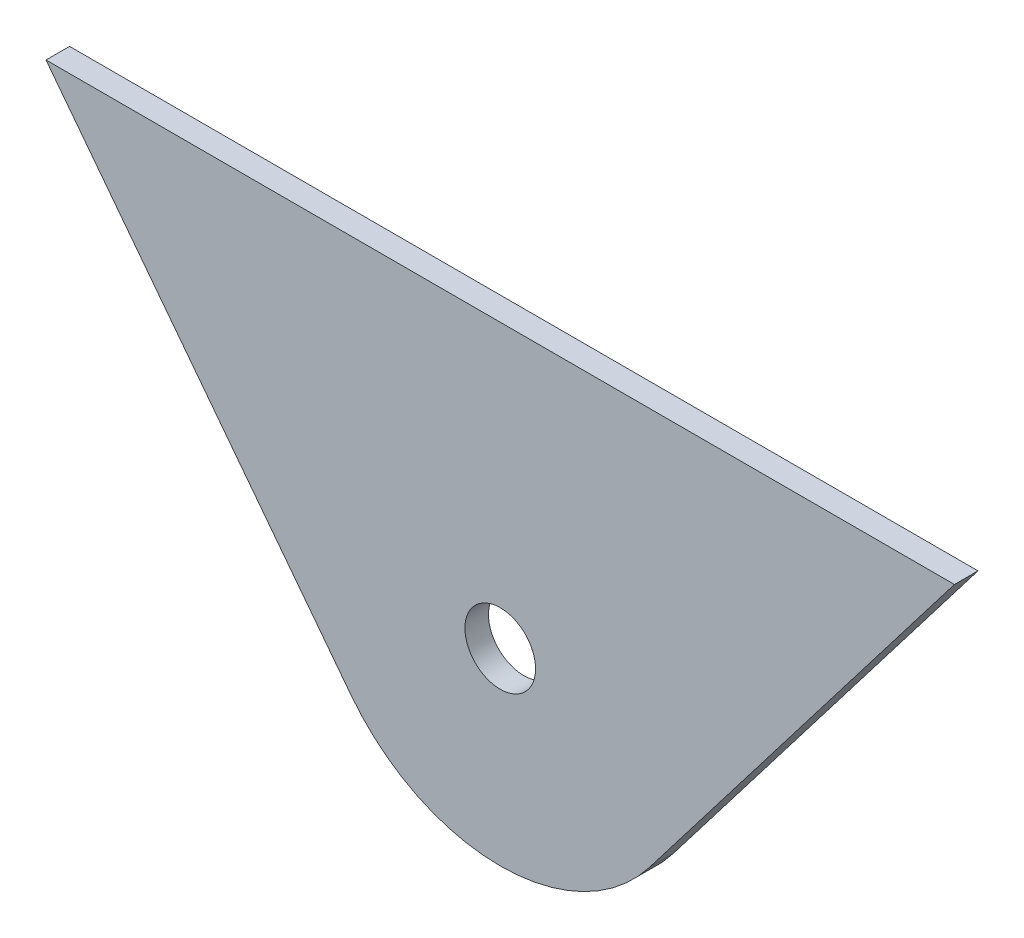
SolidWorks part; units mm, degrees
ref_plane "Front Plane" through (0, 0, 0) normal (0, 0, 1) x (1, 0, 0)
ref_plane "Top Plane" through (0, 0, 0) normal (0, 1, 0) x (1, 0, 0)
ref_plane "Right Plane" through (0, 0, 0) normal (1, 0, 0) x (0, 0, -1)
ref_axis "Suspension pivot point" through (0, 0, -0.1588) along (0, 0, 1)
sketch "Sketch1" plane through (0, 0, 0) normal (0, 0, 1) x (1, 0, 0)
  line L0 (-20.1512, -15.4625) -> (-61.2512, 38.1)
  line L1 (-61.2512, 38.1) -> (61.2512, 38.1)
  line L2 (61.2512, 38.1) -> (20.1512, -15.4625)
  line L3 (0, -25.4) -> (0, 38.1) construction
  arc A0 (-20.1512, -15.4625) -> (20.1512, -15.4625) centre (0, 0) ccw
  dimension "D1" = 25.4
  dimension "D2" = 75
  dimension "D3" = 63.5
extrude "Boss-Extrude1" add sketch "Sketch1" along normal blind 3.175
sketch "Sketch2" plane through (0, 0, 3.175) normal (0, 0, 1) x (1, 0, 0)
  circle A0 centre (0, 0) radius 4.7625
  dimension "D1" = 9.525
extrude "Cut-Extrude1" cut sketch "Sketch2" against normal through all
